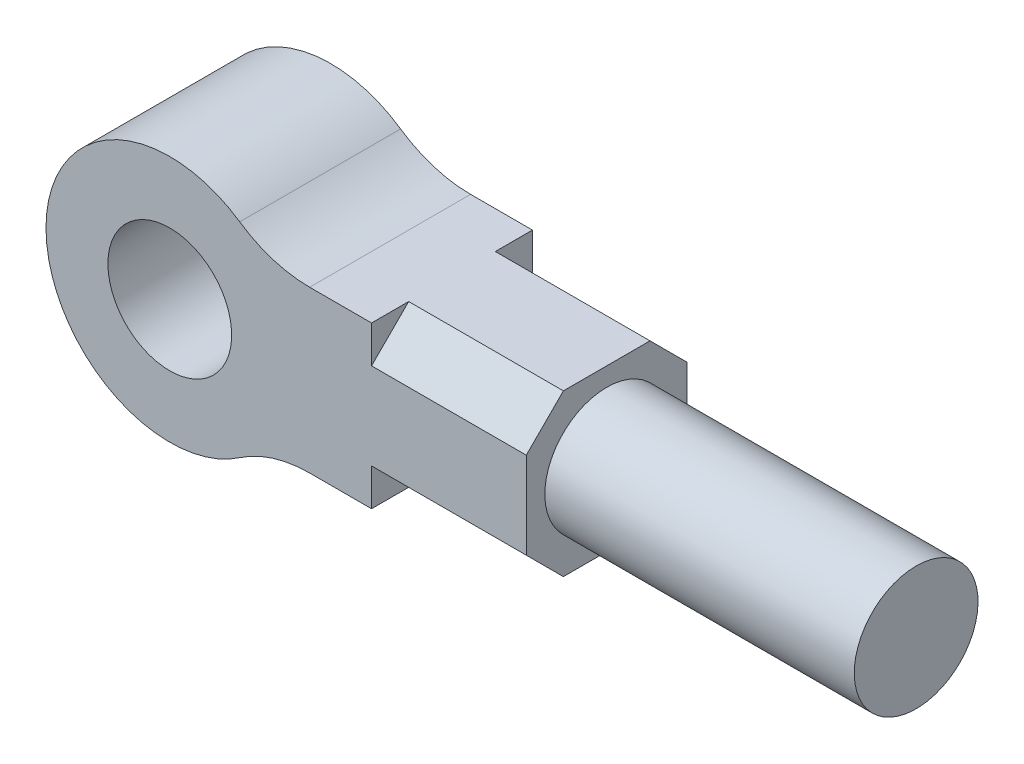
SolidWorks part; units mm, degrees
ref_plane "Front Plane" through (0, 0, 0) normal (0, 0, 1) x (1, 0, 0)
ref_plane "Top Plane" through (0, 0, 0) normal (0, 1, 0) x (1, 0, 0)
ref_plane "Right Plane" through (0, 0, 0) normal (1, 0, 0) x (0, 0, -1)
sketch "Sketch1" plane through (0, 0, 0) normal (0, 0, 1) x (1, 0, 0)
  line L0 (57.6053, 13) -> (57.6053, -13)
  line L1 (22.6053, -13) -> (57.6053, -13)
  line L2 (22.6053, 13) -> (57.6053, 13)
  arc A0 (11.3027, 16.5) -> (11.3027, -16.5) centre (0, 0) ccw
  circle A1 centre (0, 0) radius 10
  arc A2 (22.6053, -13) -> (11.3027, -16.5) centre (22.6053, -33) ccw
  arc A3 (22.6053, 13) -> (11.3027, 16.5) centre (22.6053, 33) cw
  dimension "D1" = 40
  dimension "D2" = 20
  dimension "D4" = 20
  dimension "D3" = 26
  dimension "D5" = 35
  dimension "D6" = 35
  dimension "D7" = 11.3027
extrude "Boss-Extrude1" add sketch "Sketch1" along normal mid plane 26
sketch "Sketch3" plane through (57.6053, 0, 0) normal (1, 0, 0) x (0, 0, -1)
  line L6 (0, 17.8594) -> (0, -16.9651) construction
  line L7 (-18.9215, 0) -> (16.7974, 0) construction
  line L17 (13, 13) -> (13, 7)
  line L18 (13, -13) -> (13, 13) construction
  line L19 (13, 13) -> (7, 13)
  line L20 (7, 13) -> (13, 7)
  line L21 (13, -7) -> (7, -13)
  line L22 (13, -13) -> (7, -13)
  line L23 (13, -13) -> (13, -7)
  line L24 (-7, -13) -> (-13, -7)
  line L25 (-13, -13) -> (-13, -7)
  line L26 (-13, -13) -> (-7, -13)
  line L27 (-13, 7) -> (-7, 13)
  line L28 (-13, 13) -> (-7, 13)
  line L29 (-13, 13) -> (-13, 7)
  circle A0 centre (0, 0) radius 10
  point P9 (0, 0)
  point P26 (0, 0)
  line M10 (13, -13) -> (13, 13)
  line M11 (13, 13) -> (-13, 13)
  line M12 (-13, 13) -> (-13, -13)
  line M13 (-13, -13) -> (13, -13)
  dimension "D1" = 20
  dimension "D2" = 6
  dimension "D3" = 6
  dimension "D4" = 4
extrude "Cut-Extrude1" cut sketch "Sketch3" against normal blind 25 contours L20 M11 M10 | L21 M10 M13 | L24 M13 M12 | L29 L27 L28 region at (57.6053, 11, -11) region at (57.6053, -11, -11) region at (57.6053, -11, 11)
extrude "Boss-Extrude2" add sketch "Sketch3<3>" along normal blind 50 contours A0 region at (57.6053, 0, 0)
sketch "Sketch3<3>" plane through (57.6053, 0, 0) normal (1, 0, 0) x (0, 0, -1) same geometry as "Sketch3"
